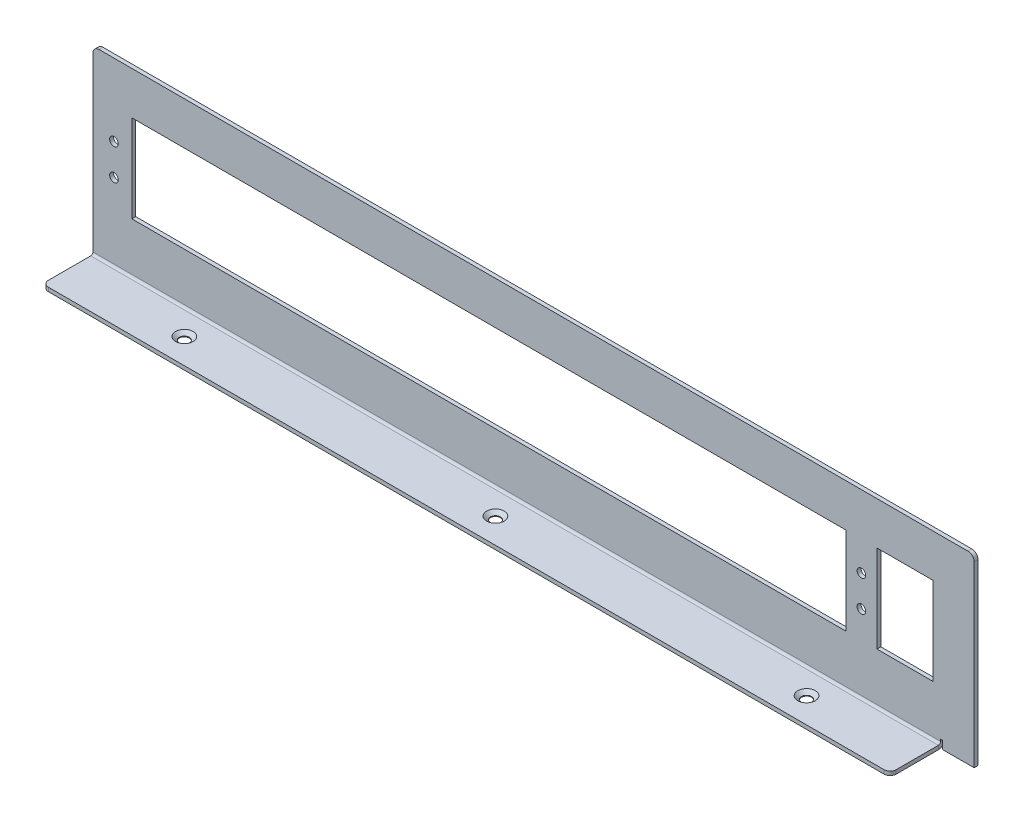
SolidWorks part; units mm, degrees
note: The reader was unsure of these and kept them because the rebuilt part matched: flange length of "Edge-Flange1".
material "6061 Alloy"
ref_plane "Front" through (0, 0, 0) normal (0, 0, 1) x (1, 0, 0)
ref_plane "Top" through (0, 0, 0) normal (0, 1, 0) x (1, 0, 0)
ref_plane "Right" through (0, 0, 0) normal (1, 0, 0) x (0, 0, -1)
sketch "Sketch2" plane through (0, 0, 0) normal (0, 0, 1) x (1, 0, 0)
  line L1 (143.89, 30.135) -> (-143.89, 30.135)
  line L2 (143.89, 30.135) -> (143.89, -30.135)
  line L3 (143.89, -30.135) -> (-143.89, -30.135)
  line L4 (-143.89, 30.135) -> (-143.89, -30.135)
  line L5 (143.89, 30.135) -> (-143.89, -30.135) construction
  line L6 (143.89, -30.135) -> (-143.89, 30.135) construction
  line L11 (-131.19, 16.165) -> (102, 16.165)
  line L12 (-131.19, 16.165) -> (-131.19, -12.415)
  line L13 (-131.19, -12.415) -> (102, -12.415)
  line L14 (102, 16.165) -> (102, -12.415)
  line L15 (112.16, 16.165) -> (130.43, 16.165)
  line L16 (112.16, 16.165) -> (112.16, -12.415)
  line L17 (112.16, -12.415) -> (130.43, -12.415)
  line L18 (130.43, 16.165) -> (130.43, -12.415)
  point P0 (0, 0)
  dimension "D1" = 287.78
  dimension "D2" = 60.27
  dimension "D3" = 13.97
  dimension "D4" = 28.58
  dimension "D5" = 233.19
  dimension "D6" = 12.7
  dimension "D7" = 10.16
  dimension "D8" = 18.27
base flange "Base-Flange1" sketch "Sketch2" thickness 1.27 reverse thickness direction no parameters "D1"=0.7366
edge flange "Edge-Flange1" sketch "Sketch9" flange angle 90 flange length 17.78 flange position material inside bend radius 0.7366 thickness 1.27 relief rectangular parameters "D6"=10
sketch "Sketch9" plane through (0, -30.135, 0) normal (0, -1, 0) x (1, 0, 0)
  line L2 (-143.89, 0) -> (-143.89, 16.51)
  line L3 (-143.89, 16.51) -> (132.97, 16.51)
  line L4 (132.97, 16.51) -> (132.97, 0)
  line L11 (-143.89, 0) -> (143.89, 0) construction
  line L12 (-143.89, 0) -> (132.97, 0)
  point P5 (-143.89, 8.255)
  dimension "D1" = 276.86
bend "EdgeBend1" bend radius 0.7366 bend angle 90 parameters "D5"=1
hole_wizard "#34 (0.111) Diameter Hole1" positions "Sketch10" profile "Sketch11" hole size "#34" standard "ANSI Inch" end condition through all
sketch "Sketch10" plane through (0, 0, 0) normal (0, 0, 1) x (1, 0, 0)
  line L0 (143.89, 30.135) -> (-143.89, 30.135) construction
  line L1 (-143.89, 30.135) -> (-143.89, -28.1284) construction
  point P0 (-137.03, 6.535)
  point P2 (-137.03, -3.625)
  point P4 (107.08, 6.535)
  point P6 (107.08, -3.625)
  dimension "D1" = 23.6
  dimension "D2" = 23.6
  dimension "D3" = 33.76
  dimension "D4" = 33.76
  dimension "D5" = 6.86
  dimension "D6" = 244.11
sketch "Sketch11" plane through (-137.03, 6.535, 0) normal (1, 0, 0) x (0, -1, 0)
  line L0 (0, 0) -> (0, 1.27)
  line L1 (0, 1.27) -> (1.4097, 1.27)
  line L2 (1.4097, 1.27) -> (1.4097, 0)
  line L5 (1.4097, 0) -> (0, 0)
  line L11 (0, -6.35) -> (0, 107.95) construction
  dimension "Thru Hole Dia." = 2.8194
  dimension "Thru Hole Depth" = 1.27
hole_wizard "CSK for #4 Flat Head Machine Screw (100)1" positions "Sketch12" profile "Sketch13" countersink size "#4" standard "ANSI Inch" end condition through all
sketch "Sketch12" plane through (0, -28.865, 0) normal (0, 1, 0) x (1, 0, 0)
  line L0 (132.97, -16.51) -> (-143.89, -16.51) construction
  line L1 (132.97, -0.7366) -> (132.97, -16.51) construction
  point P0 (97.41, -8.25)
  dimension "D1" = 8.26
  dimension "D2" = 35.56
sketch "Sketch13" plane through (97.41, -28.865, 8.25) normal (1, 0, 0) x (0, 0, 1)
  line L0 (0, 0) -> (0, 1.27)
  line L1 (0, 1.27) -> (1.6319, 1.27)
  line L2 (1.6319, 1.27) -> (1.6319, 1.0284)
  line L3 (1.6319, 1.0284) -> (2.8575, 0)
  line L5 (2.8575, 0) -> (0, 0)
  line L6 (-1.632, 1.0284) -> (-2.8575, 0) construction
  line L11 (0, -6.35) -> (0, 107.95) construction
  dimension "Thru Hole Dia." = 3.2639
  dimension "Thru Hole Depth" = 1.27
  dimension "Near C'Sink Dia." = 5.715
  dimension "Near C'Sink Angle" = 100
pattern_linear "LPattern1" count 3 spacing 101.6 along (-1, 0, 0) of "CSK for #4 Flat Head Machine Screw (100)1"
fillet "Fillet1" radius 2 4 edges at (-143.89, 30.135, -0.635) (143.89, 30.135, -0.635) (132.97, -29.5, 16.51) (-143.89, -29.5, 16.51)
sketch "Bend-Lines1" [suppressed] plane through (0, 0, 0) normal (0, 1, 0) x (1, 0, 0)
sketch "Bounding-Box1" [suppressed] plane through (0, 0, 0) normal (0, 1, 0) x (1, 0, 0)
sheet metal parameters "Sheet-Metal2" thickness 1.27 parameters "D1"=0.7366
flat pattern "Flat-Pattern2" [suppressed]
sketch "Bend-Lines2" plane through (0, 0, 0) normal (0, 1, 0) x (1, 0, 0)
sketch "Bounding-Box2" [suppressed] plane through (0, 0, 0) normal (0, 1, 0) x (1, 0, 0)
sheet metal parameters "Sheet-Metal3" thickness 1.27 parameters "D1"=0.7366
flat pattern "Flat-Pattern2" [suppressed]
sketch "Bend-Lines2" plane through (0, 0, 0) normal (0, 1, 0) x (1, 0, 0)
sketch "Bounding-Box2" [suppressed] plane through (0, 0, 0) normal (0, 1, 0) x (1, 0, 0)
bend of the flat pattern "Flatten-<EdgeBend1>1"
sheet metal parameters "Sheet-Metal4" thickness 1.27 parameters "D1"=0.7366
flat pattern "Flat-Pattern2" [suppressed]
sketch "Bend-Lines2" plane through (0, 0, 0) normal (0, 1, 0) x (1, 0, 0)
sketch "Bounding-Box2" [suppressed] plane through (0, 0, 0) normal (0, 1, 0) x (1, 0, 0)
bend of the flat pattern "Flatten-<EdgeBend1>1"
sheet metal parameters "Sheet-Metal5" thickness 1.27 parameters "D1"=0.7366
flat pattern "Flat-Pattern2" [suppressed]
sketch "Bend-Lines2" plane through (0, 0, 0) normal (0, 1, 0) x (1, 0, 0)
sketch "Bounding-Box2" [suppressed] plane through (0, 0, 0) normal (0, 1, 0) x (1, 0, 0)
bend of the flat pattern "Flatten-<EdgeBend1>1"
sheet metal parameters "Sheet-Metal6" thickness 1.27 parameters "D1"=0.7366
flat pattern "Flat-Pattern2" [suppressed]
sketch "Bend-Lines2" plane through (0, 0, 0) normal (0, 0, 1) x (1, 0, 0)
  line L0 (-143.89, -29.2057) -> (132.97, -29.2057) construction
  line L1 (-143.89, -29.2057) -> (132.97, -29.2057) construction
sketch3d "Bounding-Box2" [suppressed]
  line L0 (143.89, -46.0563, -1.27) -> (-143.89, -46.0563, -1.27) construction
  line L1 (143.89, 30.135, -1.27) -> (-143.89, 30.135, -1.27) construction
  line L2 (143.89, -46.0563, -1.27) -> (143.89, 30.135, -1.27) construction
  line L3 (-143.89, -46.0563, -1.27) -> (-143.89, 30.135, -1.27) construction
bend of the flat pattern "Flatten-<EdgeBend1>1"
